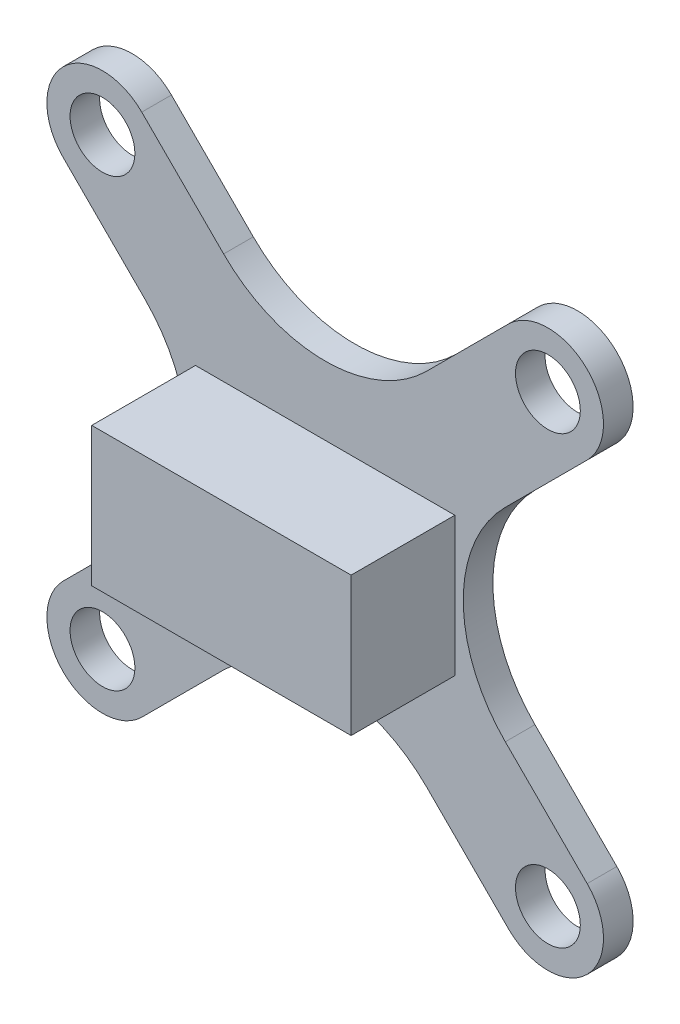
SolidWorks part; units mm, degrees
ref_plane "Front Plane" through (0, 0, 0) normal (0, 0, 1) x (1, 0, 0)
ref_plane "Top Plane" through (0, 0, 0) normal (0, 1, 0) x (1, 0, 0)
ref_plane "Right Plane" through (0, 0, 0) normal (1, 0, 0) x (0, 0, -1)
sketch "Sketch1" plane through (0, 0, 0) normal (0, 0, 1) x (1, 0, 0)
  line L0 (0, 28.0212) -> (0, -27.4834) construction
  line L1 (-27.2065, 0) -> (32.8072, 0) construction
  line L2 (-9.7227, 5.4801) -> (-14.1421, 9.8995)
  line L3 (9.7227, 5.4801) -> (14.1421, 9.8995)
  line L4 (-9.8995, 14.1421) -> (-5.4801, 9.7227)
  line L5 (0, 0) -> (-32.2659, 32.2659) construction
  line L6 (9.8995, 14.1421) -> (5.4801, 9.7227)
  line L7 (-9.7227, -5.4801) -> (-14.1421, -9.8995)
  line L8 (9.7227, -5.4801) -> (14.1421, -9.8995)
  line L9 (9.8995, -14.1421) -> (5.4801, -9.7227)
  line L10 (-9.8995, -14.1421) -> (-5.4801, -9.7227)
  line L12 (-7, 3.75) -> (7, 3.75)
  line L13 (-7, 3.75) -> (-7, -3.75)
  line L14 (-7, -3.75) -> (7, -3.75)
  line L15 (7, 3.75) -> (7, -3.75)
  line L16 (-7, 3.75) -> (7, -3.75) construction
  line L17 (-7, -3.75) -> (7, 3.75) construction
  line L18 (-2.5, 2) -> (2.5, 2)
  line L19 (-2.5, 2) -> (-2.5, -2)
  line L20 (-2.5, -2) -> (2.5, -2)
  line L21 (2.5, 2) -> (2.5, -2)
  line L22 (-2.5, 2) -> (2.5, -2) construction
  line L23 (-2.5, -2) -> (2.5, 2) construction
  circle A0 centre (0, 0) radius 17 construction
  circle A1 centre (-12.0208, 12.0208) radius 1.75
  arc A2 (-14.1421, 9.8995) -> (-9.8995, 14.1421) centre (-12.0208, 12.0208) cw
  circle A3 centre (12.0208, 12.0208) radius 1.75
  arc A4 (14.1421, 9.8995) -> (9.8995, 14.1421) centre (12.0208, 12.0208) ccw
  arc A5 (-14.1421, -9.8995) -> (-9.8995, -14.1421) centre (-12.0208, -12.0208) ccw
  circle A6 centre (-12.0208, -12.0208) radius 1.75
  arc A7 (14.1421, -9.8995) -> (9.8995, -14.1421) centre (12.0208, -12.0208) cw
  circle A8 centre (12.0208, -12.0208) radius 1.75
  arc A9 (-5.4801, 9.7227) -> (5.4801, 9.7227) centre (0, 15.2028) ccw
  arc A11 (-5.4801, -9.7227) -> (5.4801, -9.7227) centre (0, -15.2028) cw
  arc A12 (9.7227, 5.4801) -> (9.7227, -5.4801) centre (15.2028, 0) ccw
  arc A13 (-9.7227, 5.4801) -> (-9.7227, -5.4801) centre (-15.2028, 0) cw
  point P41 (0, 7.4528)
  dimension "D3" = 34
  dimension "D4" = 3.5
  dimension "D5" = 15.5
  dimension "D6" = 14.9056
  dimension "D1" = 6
  dimension "D2" = 45
  dimension "D7" = 14
  dimension "D8" = 7.5
  dimension "D9" = 5
  dimension "D10" = 4
extrude "Boss-Extrude1" add sketch "Sketch1" along normal blind 1.6 contours L2 A13 L7 A5 L10 A11 L9 A7 L8 A12 L3 A4 L6 A9 L4 A2 A6 L12 L15 L14 L13 A1 A3 A8 | L15 L12 L13 L14 region at (-11.632, 7.9902, 0) region at (0, 3.5912, 0)
extrude "Boss-Extrude2" add sketch "Sketch1<3>" along normal blind 7.2 contours L15 L12 L13 L14 | L19 L20 L21 L18 region at (0, 3.5912, 0)
sketch "Sketch1<3>" plane through (0, 0, 0) normal (0, 0, 1) x (1, 0, 0) same geometry as "Sketch1"
extrude "Boss-Extrude3" add sketch "Sketch1<5>" against normal blind 1.7 contours L21 L18 L19 L20 region at (0, 0, 0)
sketch "Sketch1<5>" plane through (0, 0, 0) normal (0, 0, 1) x (1, 0, 0) same geometry as "Sketch1"
